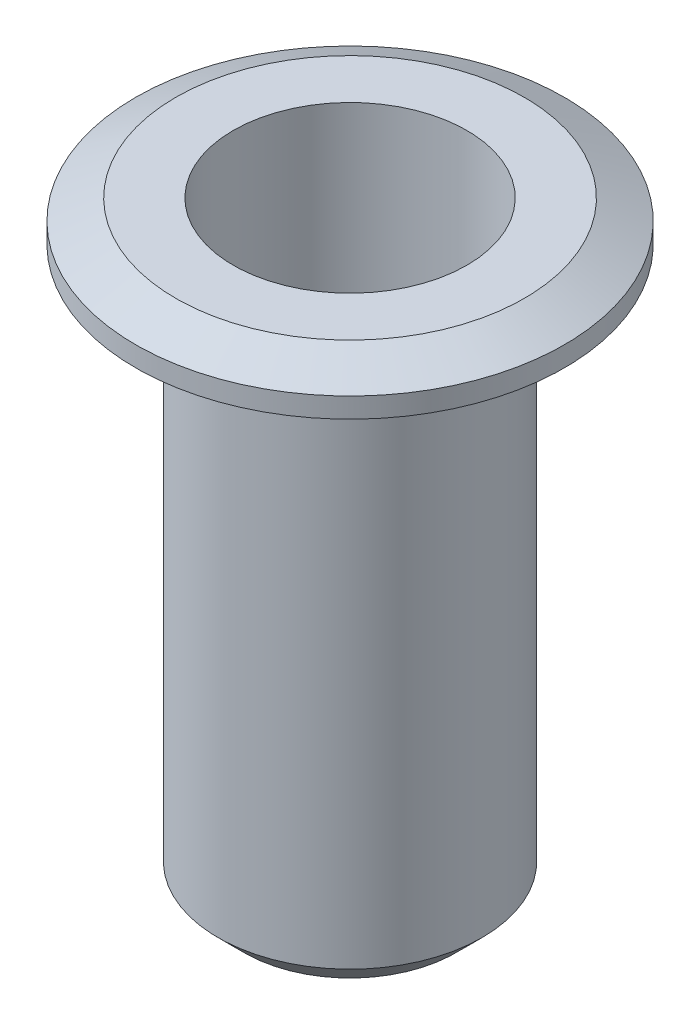
SolidWorks part; units mm, degrees
ref_plane "Front Plane" through (0, 0, 0) normal (0, 0, 1) x (1, 0, 0)
ref_plane "Top Plane" through (0, 0, 0) normal (0, 1, 0) x (1, 0, 0)
ref_plane "Right Plane" through (0, 0, 0) normal (1, 0, 0) x (0, 0, -1)
sketch "Sketch1" plane through (0, 0, 0) normal (0, 0, 1) x (1, 0, 0)
  line L0 (-3.175, -13.8236) -> (-2.546, -14.4526)
  line L1 (-2.8099, -4.8006) -> (-1.9169, -4.8006) construction
  line L2 (-1.9169, -4.8006) -> (-1.9169, -5.6936) construction
  line L3 (-2.546, -14.4526) -> (-2.413, -14.4526)
  line L4 (5.1562, 0) -> (4.191, 0) construction
  line L5 (-2.413, -14.4526) -> (-1.9169, -13.9565)
  line L6 (5.1562, -0.4826) -> (5.1562, 0) construction
  line L7 (-1.9169, -13.9565) -> (-1.9169, -5.6936)
  line L8 (3.175, -14.4526) -> (2.546, -14.4526) construction
  line L9 (-1.9169, -5.6936) -> (-2.8099, -4.8006)
  line L10 (1.9169, -14.4526) -> (1.9169, -13.9565) construction
  line L11 (-2.8099, -4.8006) -> (-2.8099, 0)
  line L12 (3.175, -13.8236) -> (3.175, -14.4526) construction
  line L13 (2.413, -14.4526) -> (1.9169, -14.4526) construction
  line L14 (-2.8099, 0) -> (-4.191, 0)
  line L15 (-4.191, 0) -> (-5.1562, -0.4826)
  line L16 (5.1562, -10.8712) -> (5.1562, -1.2192) construction
  line L17 (-5.1562, -0.4826) -> (-5.1562, -0.9652)
  line L18 (5.1562, -0.9652) -> (3.175, -0.9652) construction
  line L19 (-5.1562, -0.9652) -> (-3.175, -0.9652)
  line L20 (-3.175, -0.9652) -> (-3.175, -13.8236)
  line L21 (0, 0) -> (0, -14.4526) construction
  line L22 (-5.1562, -0.9652) -> (-5.1562, 0) construction
  line L23 (-5.1562, 0) -> (-4.191, 0) construction
  line L24 (-3.175, -13.8236) -> (-3.175, -14.4526) construction
  line L25 (-3.175, -14.4526) -> (-2.546, -14.4526) construction
  line L26 (-2.413, -14.4526) -> (-1.9169, -14.4526) construction
  line L27 (-1.9169, -14.4526) -> (-1.9169, -13.9565) construction
  line L28 (-1.9169, -14.4526) -> (0, -14.4526) construction
  line L29 (5.1562, -0.4826) -> (5.1562, -0.9652) construction
  line L30 (-2.546, -14.4526) -> (-1.9169, -14.4526) construction
  line L32 (0, 0) -> (-2.8099, 0) construction
  dimension "D7" = 3.8338
  dimension "D8" = 45
  dimension "D12" = 9.652
  dimension "D2" = 5.6197
revolve "Revolve1" add sketch "Sketch1" angle 360 about L21
sketch "Sketch2" plane through (0, -14.4526, 0) normal (0, -1, 0) x (1, 0, 0)
  circle A1 centre (0, 0) radius 2.413
  point P1 (2.413, 0)
  dimension "D1" = 4.826
ref_plane "Plane1" through (-3.175, 0, 0) normal (1, 0, 0) x (0, 0, -1)
curve "Helix/Spiral1" pitch 0.7937 height 22.2608 radius 2.413 centre (0, -14.4526, 0) axis (0, 1, 0) start towards (1, 0, 0) parameters "Height"=22.2608, "Pitch"=0.7937
sketch "Sketch3" plane through (0, 0, 0) normal (0, 0, 1) x (1, 0, 0)
  line L0 (1.8115, -14.1053) -> (1.8115, -14.8991) construction
  line L1 (1.8115, -14.8991) -> (2.4989, -14.5022) construction
  line L2 (1.8115, -14.1053) -> (2.4989, -14.5022) construction
  line L3 (1.8974, -14.1549) -> (1.8974, -14.8495) construction
  line L6 (1.8115, -14.5022) -> (1.8974, -14.5022) construction
  line L8 (2.413, -14.5022) -> (2.4989, -14.5022) construction
  line L9 (2.413, -14.4526) -> (2.413, -14.5518) construction
  line L11 (1.8545, -14.1301) -> (1.8545, -14.8743)
  line L12 (1.8545, -14.8743) -> (2.413, -14.5518)
  line L14 (2.413, -14.4526) -> (1.8545, -14.1301)
  arc A0 (2.413, -14.5518) -> (2.413, -14.4526) centre (2.3844, -14.5022) ccw
  point P13 (1.8545, -14.5022)
  dimension "D1" = 0.7937
  dimension "D2" = 0.0992
sweep "Cut-Sweep1" cut profiles "Sketch3" path "Helix/Spiral1"
ref_plane "Plane2" [suppressed] through (0, -1.4478, 0) normal (0, -1, 0) x (1, 0, 0)
sketch "Sketch5" [suppressed] plane through (0, -1.4478, 0) normal (0, -1, 0) x (1, 0, 0)
  circle A0 centre (0, 0) radius 4.953
  point P3 (-4.953, 0)
extrude "Extrude2" [suppressed] cut sketch "Sketch5" along normal blind 3.5814
pattern_linear "LPattern1" [suppressed] count 2 spacing 3.5814 along (0, 1, 0) of bodies 117
delete or keep bodies "Body-Delete1" [suppressed] type delete bodies bodies 117
combine bodies "Combine1" [suppressed] operation type add bodies to combine 118 119
sketch "Sketch6" [suppressed] plane through (0, 0, 0) normal (0, 0, 1) x (1, 0, 0)
  line L0 (-4.953, -1.4478) -> (-4.445, -1.4478)
  line L1 (-4.445, -1.4478) -> (-4.445, -2.9718)
  line L2 (-4.445, -2.9718) -> (-4.953, -2.9718)
  line L3 (-4.445, -5.842) -> (-4.445, 0) construction
  line L4 (-6.985, -1.4478) -> (6.985, -1.4478) construction
  line L5 (-4.953, -0.762) -> (-4.953, -14.2081) construction
  line L6 (0, 0) -> (0, -15.494) construction
  line L7 (0, 0) -> (0, -15.494) construction
  arc A0 (-4.953, -1.4478) -> (-4.953, -2.9718) centre (-4.953, -2.2098) ccw
  dimension "D1" = 1.524
revolve "Revolve2" [suppressed] add sketch "Sketch6" angle 360 about L7
equation "\"Height@Helix/Spiral1\" = \"Body Lg@Sketch1\" + \"Pitch@Helix/Spiral1\" +  (  pi  / 10 ) "
equation "\"D1@Sketch3\" = \"Pitch@Helix/Spiral1\""
equation "\"D2@Sketch3\" = \"D1@Sketch3\" / 8"
equation "\"D1@Extrude2\" = \"D1@Sketch1\""
equation "\"D3@LPattern1\" = \"D1@Extrude2\""
equation "\"D7@Sketch1\" = \"Thread Dia@Sketch1\" -  ( \"Pitch@Helix/Spiral1\" )  * 1.25"
equation "\"D2@Sketch1\" =  \"Thread Dia@Sketch1\" + ( \"Pitch@Helix/Spiral1\" ) * 1"
equation "\"D12@Sketch1\" = \"Max Installed Lg@Sketch1\""
equation "\"D1@Sketch2\" = \"Thread Dia@Sketch1\""
